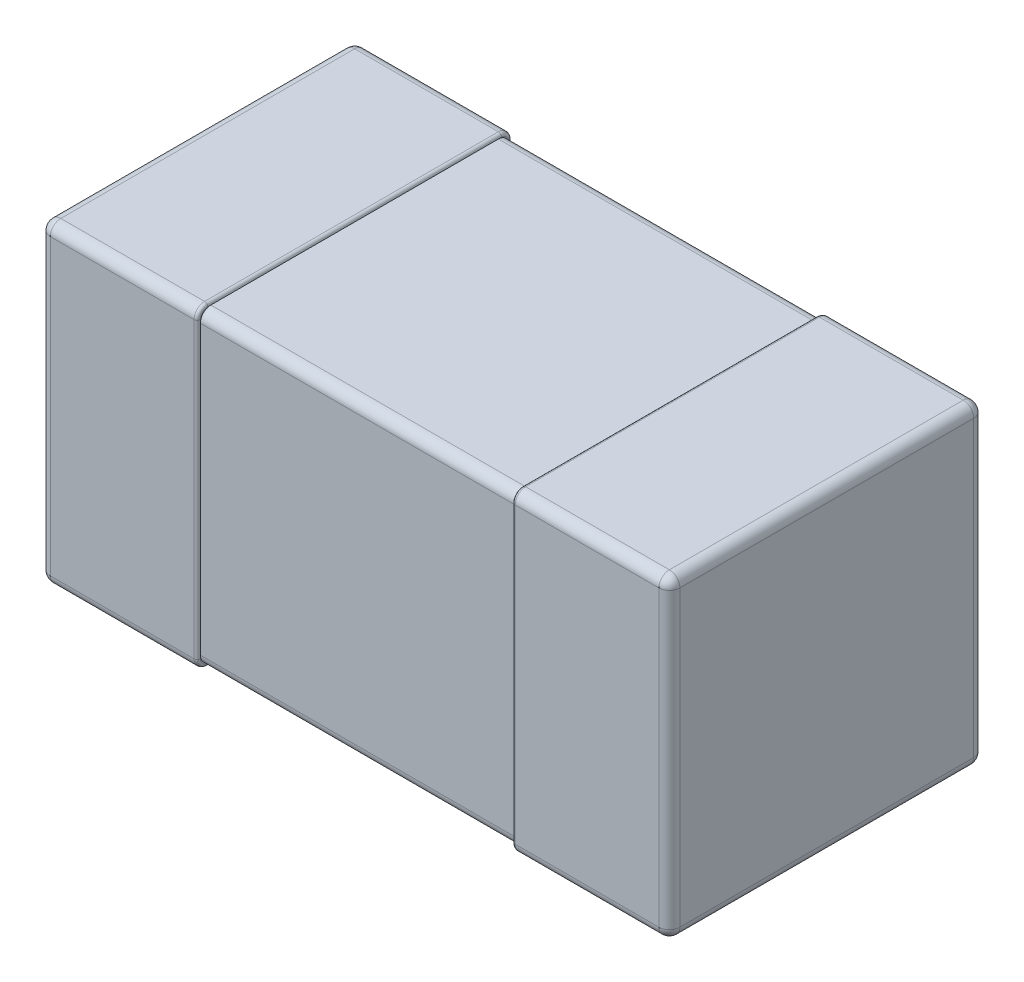
SolidWorks part; units mm, degrees
ref_plane "Top Plane" through (0, 0, 0) normal (0, 0, 1) x (1, 0, 0)
ref_plane "Front Plane" through (0, 0, 0) normal (0, 1, 0) x (1, 0, 0)
ref_plane "Side Plane" through (0, 0, 0) normal (1, 0, 0) x (0, 0, -1)
sketch "Sketch1" plane through (0, 0, 0) normal (0, 0, 1) x (1, 0, 0)
  line L1 (-0.3, 0.15) -> (0.3, 0.15)
  line L2 (-0.3, 0.15) -> (-0.3, -0.15)
  line L3 (-0.3, -0.15) -> (0.3, -0.15)
  line L4 (0.3, 0.15) -> (0.3, -0.15)
  dimension "D1" = 0.6
  dimension "D2" = 0.3
  dimension "D3" = 0.3
  dimension "D4" = 0.15
extrude "All body" add sketch "Sketch1" along normal blind 0.3
sketch "Sketch2" plane through (0, 0, 0) normal (1, 0, 0) x (0, 0, -1)
  line L14 (-0.003, 0.147) -> (-0.297, 0.147)
  line L15 (-0.003, -0.147) -> (-0.003, 0.147)
  line L16 (-0.297, -0.147) -> (-0.003, -0.147)
  line L17 (-0.297, 0.147) -> (-0.297, -0.147)
  line L18 (-0.003, 0.147) -> (-0.297, 0.147)
  line L19 (-0.003, -0.147) -> (-0.003, 0.147)
  line L20 (-0.297, -0.147) -> (-0.003, -0.147)
  line L21 (-0.297, 0.147) -> (-0.297, -0.147)
  dimension "D1" = 0.003
extrude "Cut out the body for pin" cut sketch "Sketch2" against normal blind 0.15 and the other way blind 0.15 flip side to cut
fillet "Body fillet" radius 0.01 4 edges at (0, 0.147, 0.003) (0, 0.147, 0.297) (0, -0.147, 0.003) (0, -0.147, 0.297)
fillet "Pin fillet a" radius 0.01 16 edges at (0.3, -0.15, 0.15) (0.3, 0, 0.3) (0.3, 0.15, 0.15) (0.3, 0, 0) (-0.3, 0.15, 0.15) (-0.3, 0, 0.3) (-0.3, -0.15, 0.15) (-0.3, 0, 0) (0.225, 0.15, 0.3) (0.225, -0.15, 0.3) (0.225, -0.15, 0) (0.225, 0.15, 0) (-0.225, 0.15, 0) (-0.225, -0.15, 0) (-0.225, 0.15, 0.3) (-0.225, -0.15, 0.3)
fillet "Pin fillet b" radius 0.003 16 edges at (0.15, -0.1471, 0.2971) (0.15, -0.15, 0.15) (0.15, -0.1471, 0.0029) (0.15, 0, 0) (0.15, 0.1471, 0.0029) (0.15, 0.15, 0.15) (0.15, 0.1471, 0.2971) (-0.15, -0.1471, 0.2971) (-0.15, -0.15, 0.15) (-0.15, -0.1471, 0.0029) (-0.15, 0, 0) (-0.15, 0.1471, 0.0029) (-0.15, 0.15, 0.15) (-0.15, 0.1471, 0.2971) (0.15, 0, 0.3) (-0.15, 0, 0.3)
